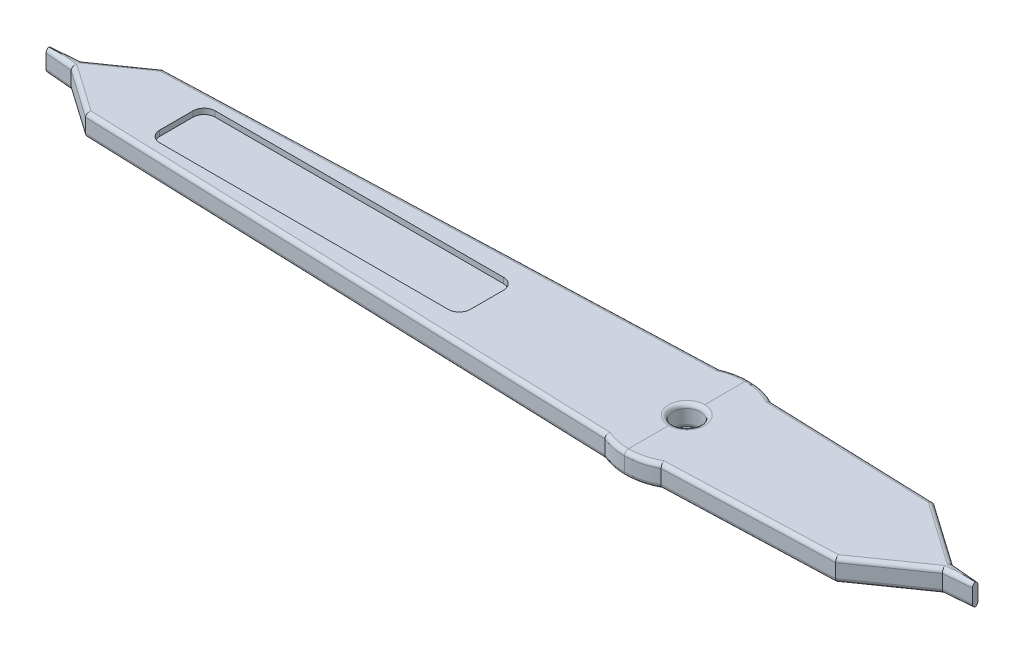
SolidWorks part; units mm, degrees
ref_plane "Front" through (0, 0, 0) normal (0, 0, 1) x (1, 0, 0)
ref_plane "Top" through (0, 0, 0) normal (0, 1, 0) x (1, 0, 0)
ref_plane "Right" through (0, 0, 0) normal (1, 0, 0) x (0, 0, -1)
sketch "Sketch1" plane through (0, 0, 0) normal (0, 1, 0) x (1, 0, 0)
  line L0 (-11.5, 0) -> (5.2, 0) construction
  line L1 (-11.5, -0.05) -> (-11.5, 0.05)
  line L2 (-11.5, 0.05) -> (-11.0019, 0.0936)
  line L3 (-11.0019, 0.0936) -> (-10.1416, 0.696)
  line L5 (3.5698, 0.8863) -> (4.7019, 0.0936)
  line L6 (4.7019, 0.0936) -> (5.2, 0.05)
  line L7 (5.2, 0.05) -> (5.2, -0.05)
  line L8 (0.5298, 0.9924) -> (3.5698, 0.8863)
  line L9 (4.7019, -0.0936) -> (5.2, -0.05)
  line L10 (3.5698, -0.8863) -> (4.7019, -0.0936)
  line L11 (0.5298, -0.9924) -> (3.5698, -0.8863)
  line L12 (-10.1416, -0.696) -> (-0.4416, -1.0347)
  line L13 (-11.0019, -0.0936) -> (-10.1416, -0.696)
  line L14 (-11.5, -0.05) -> (-11.0019, -0.0936)
  line L15 (-10.1416, 0.696) -> (-0.4416, 1.0347)
  arc A0 (-0.4416, -1.0347) -> (0.5298, -0.9924) centre (0, 0) ccw
  circle A1 centre (0, 0) radius 0.25
  arc A2 (0.5298, 0.9924) -> (-0.4416, 1.0347) centre (0, 0) ccw
  point P15 (-1.025, 0.8786)
  point P22 (1.2076, 0.4576)
  point P23 (0.7596, 0.8299)
  point P24 (0.6372, 0.9272)
  dimension "D9" = 2.25
  dimension "D10" = 0.5
  dimension "D1" = 11.5
  dimension "D2" = 5.2
  dimension "D3" = 0.05
  dimension "D4" = 147
  dimension "D5" = 150
  dimension "D6" = 95
  dimension "D7" = 150
  dimension "D8" = 0.5
  dimension "D11" = 147
  dimension "D12" = 9.7
  dimension "D13" = 3.04
extrude "Boss-Extrude1" add sketch "Sketch1" along normal mid plane 0.4
fillet "Fillet1" radius 0.075 30 edges at (-5.2916, 0.2, -0.8653) (0.0489, 0.2, -1.1239) (2.0498, 0.2, -0.9393) (4.1359, 0.2, -0.4899) (4.951, 0.2, -0.0718) (4.951, 0.2, 0.0718) (4.1359, 0.2, 0.4899) (2.0498, 0.2, 0.9393) (0.0489, 0.2, 1.1239) (-5.2916, 0.2, 0.8653) (-10.5717, 0.2, 0.3948) (-11.251, 0.2, 0.0718) (-11.251, 0.2, -0.0718) (-10.5717, 0.2, -0.3948) (0, -0.2, 0.25) (-11.251, -0.2, -0.0718) (-11.251, -0.2, 0.0718) (-10.5717, -0.2, 0.3948) (-5.2916, -0.2, 0.8653) (0.0489, -0.2, 1.1239) (2.0498, -0.2, 0.9393) (4.1359, -0.2, 0.4899) (4.951, -0.2, 0.0718) (4.951, -0.2, -0.0718) (4.1359, -0.2, -0.4899) (2.0498, -0.2, -0.9393) (0.0489, -0.2, -1.1239) (-5.2916, -0.2, -0.8653) (-10.5717, -0.2, -0.3948) (0, 0.2, 0.25)
sketch "Sketch2" plane through (0, 0.2, 0) normal (0, 1, 0) x (1, 0, 0)
  line L1 (-9, 0.5) -> (-3.8, 0.5)
  line L2 (-9.2, 0.3) -> (-9.2, -0.3)
  line L3 (-9, -0.5) -> (-3.8, -0.5)
  line L4 (-3.6, 0.3) -> (-3.6, -0.3)
  arc A0 (-3.8, 0.5) -> (-3.6, 0.3) centre (-3.8, 0.3) cw
  arc A1 (-9.2, -0.3) -> (-9, -0.5) centre (-9, -0.3) ccw
  arc A2 (-3.8, -0.5) -> (-3.6, -0.3) centre (-3.8, -0.3) ccw
  arc A3 (-9, 0.5) -> (-9.2, 0.3) centre (-9, 0.3) ccw
  point P4 (-3.6, 0)
  point P8 (-3.6, 0.5)
  point P11 (-9.2, -0.5)
  point P14 (-3.6, -0.5)
  dimension "D4" = 0.2
  dimension "D5" = 0.2
  dimension "D1" = 5.6
  dimension "D2" = 3.6
  dimension "D3" = 1
extrude "Cut-Extrude1" cut sketch "Sketch2" against normal blind 0.1
sketch "Sketch3" plane through (0, 0.2, 0) normal (0, 1, 0) x (1, 0, 0)
  line L0 (0, 2.6531) -> (0, -2.6531)
split line "Split Line1"
